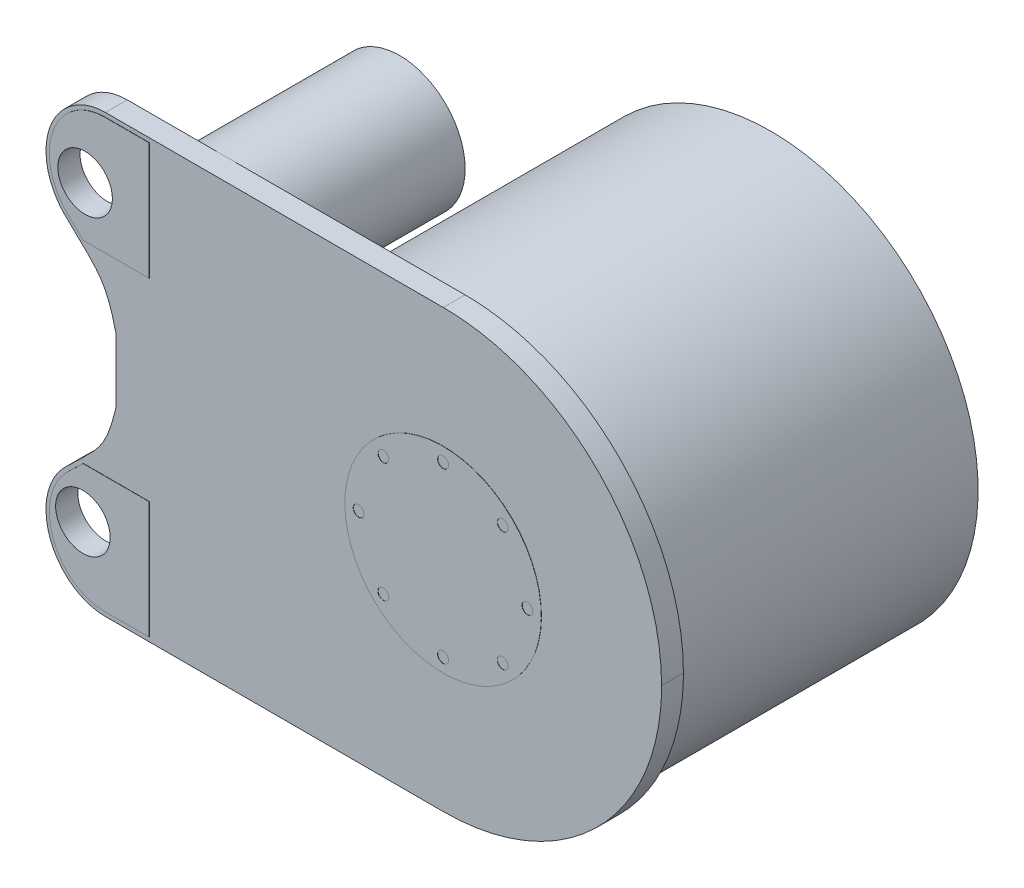
SolidWorks part; units mm, degrees
ref_plane "Plano frontal" through (0, 0, 0) normal (0, 0, 1) x (1, 0, 0)
ref_plane "Plano superior" through (0, 0, 0) normal (0, 1, 0) x (1, 0, 0)
ref_plane "Plano direito" through (0, 0, 0) normal (1, 0, 0) x (0, 0, -1)
sketch "Esboço1" plane through (0, 0, 0) normal (0, 0, 1) x (1, 0, 0)
  line L0 (-10.9, 1.5) -> (-10.9, 1.4998)
  line L1 (-10.9, -1.4998) -> (-10.9, -1.5)
  line L2 (-11.375, -9.9996) -> (-10.1, -9.9996)
  line L3 (-10.1, -9.9996) -> (4.1, -9.9996)
  line L4 (4.1, 9.9996) -> (-10.1, 9.9996)
  line L5 (-10.1, 9.9996) -> (-11.375, 9.9996)
  ellipse E0 centre (4.1, -0.0004) end of major axis (4.1, 9.4996) minor radius 9.5
  ellipse E1 centre (-12.3, 6.7497) end of major axis (-12.3, 7.9997) minor radius 1.25
  ellipse E2 centre (-12.4, -6.7497) end of major axis (-11.15, -6.7497) minor radius 1.2499
  ellipse E5 centre (4.1, -0.0004) end of major axis (4.1, 8.4996) minor radius 8.5
  spline S0 degree 3 poles (-11.375, 9.9996) (-12.8799, 9.9996) (-14.1, 8.7075) (-14.1, 7.1137) knots 0 0 0 0 0.05 0.05 0.05 0.05
  spline S1 degree 3 poles (-14.1, 7.1137) (-14.1, 6.3284) (-13.8037, 5.6164) (-13.3233, 5.0962) knots 0.05 0.05 0.05 0.05 0.1 0.1 0.1 0.1
  spline S2 degree 3 poles (-13.3233, 5.0962) (-13.3196, 5.092) (-13.3154, 5.0875) (-13.3114, 5.0835) knots 0.1 0.1 0.1 0.1 0.15 0.15 0.15 0.15
  spline S3 degree 3 poles (-13.3114, 5.0835) (-13.2765, 5.0461) (-13.2405, 5.0095) (-13.2036, 4.9741) knots 0.15 0.15 0.15 0.15 0.2 0.2 0.2 0.2
  spline S4 degree 3 poles (-13.2036, 4.9741) (-11.7596, 3.5417) (-11.3715, 3.4497) (-10.9, 1.5) knots 0.2 0.2 0.2 0.2 0.25 0.25 0.25 0.25
  spline S5 degree 3 poles (-10.9, 1.4998) (-10.9, 0.5) (-10.9, -0.5) (-10.9, -1.4998) knots 0.3 0.3 0.3 0.3 0.35 0.35 0.35 0.35
  spline S6 degree 3 poles (-10.9, -1.5) (-11.3712, -3.4492) (-11.761, -3.5431) (-13.2036, -4.9741) knots 0.4 0.4 0.4 0.4 0.45 0.45 0.45 0.45
  spline S7 degree 3 poles (-13.2036, -4.9741) (-13.2369, -5.006) (-13.2695, -5.0389) (-13.3011, -5.0725) knots 0.45 0.45 0.45 0.45 0.5 0.5 0.5 0.5
  spline S8 degree 3 poles (-13.3011, -5.0725) (-13.3105, -5.0824) (-13.3196, -5.0921) (-13.3287, -5.1021) knots 0.5 0.5 0.5 0.5 0.55 0.55 0.55 0.55
  spline S9 degree 3 poles (-13.3287, -5.1021) (-13.8059, -5.6217) (-14.1, -6.3313) (-14.1, -7.1137) knots 0.55 0.55 0.55 0.55 0.6 0.6 0.6 0.6
  spline S10 degree 3 poles (-14.1, -7.1137) (-14.1, -8.7075) (-12.8799, -9.9996) (-11.375, -9.9996) knots 0.6 0.6 0.6 0.6 0.65 0.65 0.65 0.65
  spline S11 degree 3 poles (4.1, -9.9996) (9.6228, -9.9996) (14.1, -5.5226) (14.1, 0) knots 0.75 0.75 0.75 0.75 0.8 0.8 0.8 0.8
  spline S12 degree 3 poles (14.1, 0) (14.1, 5.5226) (9.6228, 9.9996) (4.1, 9.9996) knots 0.8 0.8 0.8 0.8 0.85 0.85 0.85 0.85
  point P56 (-6.9, 6.9997)
  ellipse B0 centre (-6.9, 6.9997) end of major axis (-3.9, 6.9997) minor radius 2.9999
  ellipse B1 centre (-6.9, 6.9997) end of major axis (-9.15, 6.9997) minor radius 2.25
sketch_block_instance "Bloco1-1"
sketch_block "Bloco1"
extrude "Ressalto-extrusão1" add sketch "Esboço1" along normal blind 1 contours L4 L5 S0 S1 S2 S3 S4 L0 S5 L1 S6 S7 S8 S9 S10 L2 L3 S11 S12
ref_plane "Plano2" through (0, 0, 1) normal (0, 0, 1) x (1, 0, 0)
sketch "Esboço3" plane through (0, 0, 1) normal (0, 0, 1) x (1, 0, 0)
  line L0 (-12.3882, 4.4299) -> (-9.3652, 4.4299)
  line L1 (-9.3652, 4.4299) -> (-9.3652, 9.8065)
  line L2 (-9.3652, 9.8065) -> (-10.2039, 9.8065)
  line L3 (-10.2039, 9.8065) -> (-11.3935, 9.8065)
  line L4 (-12.3882, -4.4299) -> (-9.3652, -4.4299)
  line L5 (-9.3652, -4.4299) -> (-9.3652, -9.8065)
  line L6 (-9.3652, -9.8065) -> (-10.2039, -9.8065)
  line L7 (-10.2039, -9.8065) -> (-11.3935, -9.8065)
  ellipse E0 centre (4.1, -0.0004) end of major axis (4.1, 4.4996) minor radius 4.5
  ellipse E1 centre (4.1, 3.8664) end of major axis (3.85, 3.8664) minor radius 0.25
  spline S0 degree 3 poles (-11.3935, 9.8065) (-12.7975, 9.8065) (-13.9358, 8.601) (-13.9358, 7.114) knots 0 0 0 0 0.1 0.1 0.1 0.1
  spline S1 degree 3 poles (-13.9358, 7.114) (-13.9358, 6.3813) (-13.6594, 5.717) (-13.2112, 5.2317) knots 0.1 0.1 0.1 0.1 0.2 0.2 0.2 0.2
  spline S2 degree 3 poles (-13.2112, 5.2317) (-13.2077, 5.2278) (-13.2038, 5.2236) (-13.2001, 5.2199) knots 0.2 0.2 0.2 0.2 0.3 0.3 0.3 0.3
  spline S3 degree 3 poles (-13.2001, 5.2199) (-13.1675, 5.185) (-13.1339, 5.1508) (-13.0995, 5.1178) knots 0.3 0.3 0.3 0.3 0.4 0.4 0.4 0.4
  spline S4 degree 3 poles (-13.0995, 5.1178) (-12.8243, 4.8448) (-12.5903, 4.624) (-12.3882, 4.4299) knots 0.4 0.4 0.4 0.4 0.5 0.5 0.5 0.5
  spline S5 degree 3 poles (-11.3935, -9.8065) (-12.7975, -9.8065) (-13.9358, -8.601) (-13.9358, -7.114) knots 0 0 0 0 0.1 0.1 0.1 0.1
  spline S6 degree 3 poles (-13.9358, -7.114) (-13.9358, -6.3813) (-13.6594, -5.717) (-13.2112, -5.2317) knots 0.1 0.1 0.1 0.1 0.2 0.2 0.2 0.2
  spline S7 degree 3 poles (-13.2112, -5.2317) (-13.2077, -5.2278) (-13.2038, -5.2236) (-13.2001, -5.2199) knots 0.2 0.2 0.2 0.2 0.3 0.3 0.3 0.3
  spline S8 degree 3 poles (-13.2001, -5.2199) (-13.1675, -5.185) (-13.1339, -5.1508) (-13.0995, -5.1178) knots 0.3 0.3 0.3 0.3 0.4 0.4 0.4 0.4
  spline S9 degree 3 poles (-13.0995, -5.1178) (-12.8243, -4.8448) (-12.5903, -4.624) (-12.3882, -4.4299) knots 0.4 0.4 0.4 0.4 0.5 0.5 0.5 0.5
  spline S10 degree 3 poles (7.011, 2.9106) (7.1086, 2.813) (7.1086, 2.6547) (7.011, 2.5571) knots 0 0 0 0 0.2 0.2 0.2 0.2
  spline S11 degree 3 poles (7.011, 2.5571) (6.9134, 2.4594) (6.7551, 2.4594) (6.6575, 2.5571) knots 0.2 0.2 0.2 0.2 0.4 0.4 0.4 0.4
  spline S12 degree 3 poles (6.6575, 2.5571) (6.5598, 2.6547) (6.5598, 2.813) (6.6575, 2.9106) knots 0.4 0.4 0.4 0.4 0.6 0.6 0.6 0.6
  spline S13 degree 3 poles (6.6575, 2.9106) (6.7551, 3.0082) (6.9134, 3.0082) (7.011, 2.9106) knots 0.6 0.6 0.6 0.6 1 1 1 1
  spline S14 degree 3 poles (8.2168, -0.0004) (8.2168, -0.1385) (8.1049, -0.2504) (7.9668, -0.2504) knots 0 0 0 0 0.2 0.2 0.2 0.2
  spline S15 degree 3 poles (7.9668, -0.2504) (7.8287, -0.2504) (7.7168, -0.1385) (7.7168, -0.0004) knots 0.2 0.2 0.2 0.2 0.4 0.4 0.4 0.4
  spline S16 degree 3 poles (7.7168, -0.0004) (7.7168, 0.1377) (7.8287, 0.2496) (7.9668, 0.2496) knots 0.4 0.4 0.4 0.4 0.6 0.6 0.6 0.6
  spline S17 degree 3 poles (7.9668, 0.2496) (8.1049, 0.2496) (8.2168, 0.1377) (8.2168, -0.0004) knots 0.6 0.6 0.6 0.6 1 1 1 1
  spline S18 degree 3 poles (7.011, -2.9114) (6.9134, -3.009) (6.7551, -3.009) (6.6575, -2.9114) knots 0 0 0 0 0.2 0.2 0.2 0.2
  spline S19 degree 3 poles (6.6575, -2.9114) (6.5598, -2.8138) (6.5598, -2.6555) (6.6575, -2.5579) knots 0.2 0.2 0.2 0.2 0.4 0.4 0.4 0.4
  spline S20 degree 3 poles (6.6575, -2.5579) (6.7551, -2.4602) (6.9134, -2.4602) (7.011, -2.5579) knots 0.4 0.4 0.4 0.4 0.6 0.6 0.6 0.6
  spline S21 degree 3 poles (7.011, -2.5579) (7.1086, -2.6555) (7.1086, -2.8138) (7.011, -2.9114) knots 0.6 0.6 0.6 0.6 1 1 1 1
  spline S22 degree 3 poles (4.1, -4.1172) (3.9619, -4.1172) (3.85, -4.0053) (3.85, -3.8672) knots 0 0 0 0 0.2 0.2 0.2 0.2
  spline S23 degree 3 poles (3.85, -3.8672) (3.85, -3.7291) (3.9619, -3.6172) (4.1, -3.6172) knots 0.2 0.2 0.2 0.2 0.4 0.4 0.4 0.4
  spline S24 degree 3 poles (4.1, -3.6172) (4.2381, -3.6172) (4.35, -3.7291) (4.35, -3.8672) knots 0.4 0.4 0.4 0.4 0.6 0.6 0.6 0.6
  spline S25 degree 3 poles (4.35, -3.8672) (4.35, -4.0053) (4.2381, -4.1172) (4.1, -4.1172) knots 0.6 0.6 0.6 0.6 1 1 1 1
  spline S26 degree 3 poles (1.189, -2.9114) (1.0914, -2.8138) (1.0914, -2.6555) (1.189, -2.5579) knots 0 0 0 0 0.2 0.2 0.2 0.2
  spline S27 degree 3 poles (1.189, -2.5579) (1.2866, -2.4602) (1.4449, -2.4602) (1.5425, -2.5579) knots 0.2 0.2 0.2 0.2 0.4 0.4 0.4 0.4
  spline S28 degree 3 poles (1.5425, -2.5579) (1.6402, -2.6555) (1.6402, -2.8138) (1.5425, -2.9114) knots 0.4 0.4 0.4 0.4 0.6 0.6 0.6 0.6
  spline S29 degree 3 poles (1.5425, -2.9114) (1.4449, -3.009) (1.2866, -3.009) (1.189, -2.9114) knots 0.6 0.6 0.6 0.6 1 1 1 1
  spline S30 degree 3 poles (-0.0168, -0.0004) (-0.0168, 0.1377) (0.0951, 0.2496) (0.2332, 0.2496) knots 0 0 0 0 0.2 0.2 0.2 0.2
  spline S31 degree 3 poles (0.2332, 0.2496) (0.3713, 0.2496) (0.4832, 0.1377) (0.4832, -0.0004) knots 0.2 0.2 0.2 0.2 0.4 0.4 0.4 0.4
  spline S32 degree 3 poles (0.4832, -0.0004) (0.4832, -0.1385) (0.3713, -0.2504) (0.2332, -0.2504) knots 0.4 0.4 0.4 0.4 0.6 0.6 0.6 0.6
  spline S33 degree 3 poles (0.2332, -0.2504) (0.0951, -0.2504) (-0.0168, -0.1385) (-0.0168, -0.0004) knots 0.6 0.6 0.6 0.6 1 1 1 1
  spline S34 degree 3 poles (1.189, 2.9106) (1.2866, 3.0082) (1.4449, 3.0082) (1.5425, 2.9106) knots 0 0 0 0 0.2 0.2 0.2 0.2
  spline S35 degree 3 poles (1.5425, 2.9106) (1.6402, 2.813) (1.6402, 2.6547) (1.5425, 2.5571) knots 0.2 0.2 0.2 0.2 0.4 0.4 0.4 0.4
  spline S36 degree 3 poles (1.5425, 2.5571) (1.4449, 2.4594) (1.2866, 2.4594) (1.189, 2.5571) knots 0.4 0.4 0.4 0.4 0.6 0.6 0.6 0.6
  spline S37 degree 3 poles (1.189, 2.5571) (1.0914, 2.6547) (1.0914, 2.813) (1.189, 2.9106) knots 0.6 0.6 0.6 0.6 1 1 1 1
extrude "Ressalto-extrusão8" add sketch "Esboço3" along normal blind 0.01
extrude "Corte-extrusão1" cut sketch "Esboço1<3>" along normal blind 1.5 contours E1 | E2
sketch "Esboço1<3>" plane through (0, 0, 0) normal (0, 0, 1) x (1, 0, 0) same geometry as "Esboço1"
extrude "Ressalto-extrusão2" add sketch "Esboço1<4>" against normal blind 14 contours E0 | E5
sketch "Esboço1<4>" plane through (0, 0, 0) normal (0, 0, 1) x (1, 0, 0) same geometry as "Esboço1"
extrude "Ressalto-extrusão3" add sketch "Esboço1<5>" against normal blind 8 contours B0 | B1
sketch "Esboço1<5>" plane through (0, 0, 0) normal (0, 0, 1) x (1, 0, 0) same geometry as "Esboço1"
extrude "Ressalto-extrusão4" add sketch "Esboço1<6>" against normal blind 11.5 contours E5
sketch "Esboço1<6>" plane through (0, 0, 0) normal (0, 0, 1) x (1, 0, 0) same geometry as "Esboço1"
extrude "Ressalto-extrusão5" add sketch "Esboço1<7>" against normal blind 6.5 contours B1
sketch "Esboço1<7>" plane through (0, 0, 0) normal (0, 0, 1) x (1, 0, 0) same geometry as "Esboço1"
sketch "Esboço4" plane through (0, 0, 0) normal (0, 0, 1) x (1, 0, 0)
  line L0 (-12.3882, 4.4299) -> (-9.3652, 4.4299)
  line L1 (-9.3652, 4.4299) -> (-9.3652, 9.8065)
  line L2 (-9.3652, 9.8065) -> (-10.2039, 9.8065)
  line L3 (-10.2039, 9.8065) -> (-11.3935, 9.8065)
  line L4 (-12.3882, -4.4299) -> (-9.3652, -4.4299)
  line L5 (-9.3652, -4.4299) -> (-9.3652, -9.8065)
  line L6 (-9.3652, -9.8065) -> (-10.2039, -9.8065)
  line L7 (-10.2039, -9.8065) -> (-11.3935, -9.8065)
  spline S0 degree 3 poles (-11.3935, 9.8065) (-12.7975, 9.8065) (-13.9358, 8.601) (-13.9358, 7.114) knots 0 0 0 0 0.1 0.1 0.1 0.1
  spline S1 degree 3 poles (-13.9358, 7.114) (-13.9358, 6.3813) (-13.6594, 5.717) (-13.2112, 5.2317) knots 0.1 0.1 0.1 0.1 0.2 0.2 0.2 0.2
  spline S2 degree 3 poles (-13.2112, 5.2317) (-13.2077, 5.2278) (-13.2038, 5.2236) (-13.2001, 5.2199) knots 0.2 0.2 0.2 0.2 0.3 0.3 0.3 0.3
  spline S3 degree 3 poles (-13.2001, 5.2199) (-13.1675, 5.185) (-13.1339, 5.1508) (-13.0995, 5.1178) knots 0.3 0.3 0.3 0.3 0.4 0.4 0.4 0.4
  spline S4 degree 3 poles (-13.0995, 5.1178) (-12.8243, 4.8448) (-12.5903, 4.624) (-12.3882, 4.4299) knots 0.4 0.4 0.4 0.4 0.5 0.5 0.5 0.5
  spline S5 degree 3 poles (-11.3935, -9.8065) (-12.7975, -9.8065) (-13.9358, -8.601) (-13.9358, -7.114) knots 0 0 0 0 0.1 0.1 0.1 0.1
  spline S6 degree 3 poles (-13.9358, -7.114) (-13.9358, -6.3813) (-13.6594, -5.717) (-13.2112, -5.2317) knots 0.1 0.1 0.1 0.1 0.2 0.2 0.2 0.2
  spline S7 degree 3 poles (-13.2112, -5.2317) (-13.2077, -5.2278) (-13.2038, -5.2236) (-13.2001, -5.2199) knots 0.2 0.2 0.2 0.2 0.3 0.3 0.3 0.3
  spline S8 degree 3 poles (-13.2001, -5.2199) (-13.1675, -5.185) (-13.1339, -5.1508) (-13.0995, -5.1178) knots 0.3 0.3 0.3 0.3 0.4 0.4 0.4 0.4
  spline S9 degree 3 poles (-13.0995, -5.1178) (-12.8243, -4.8448) (-12.5903, -4.624) (-12.3882, -4.4299) knots 0.4 0.4 0.4 0.4 0.5 0.5 0.5 0.5
extrude "Ressalto-extrusão11" add sketch "Esboço4" against normal blind 0.01
extrude "Corte-extrusão4" cut sketch "Esboço1<9>" against normal blind 0.5 contours E1 | E2
sketch "Esboço1<9>" plane through (0, 0, 0) normal (0, 0, 1) x (1, 0, 0) same geometry as "Esboço1"
sketch "Sketch1" plane through (0, 0, 0) normal (0, 0, -1) x (-1, 0, 0)
  point P0 (12.3, 6.7497)
  point P1 (12.4, -6.7497)
sketch "Sketch2" plane through (0, 0, 1) normal (0, 0, 1) x (1, 0, 0)
  point P0 (-12.4, -6.7497)
  point P1 (-12.3, 6.7497)
ref_axis "Axis1" through (-12.4, -6.7497, 0) along (0, 0, 1)
ref_axis "Axis2" through (-12.3, 6.7497, 0) along (0, 0, 1)
sketch "Sketch3" plane through (0, 0, -14) normal (0, 0, -1) x (-1, 0, 0)
  point P0 (-4.1, -0.0004)
sketch "Sketch4" plane through (0, 0, -11.5) normal (0, 0, -1) x (-1, 0, 0)
  point P0 (-4.1, -0.0004)
ref_axis "Axis3" through (4.1, -0.0004, -14) along (0, 0, 1)
sketch "Sketch5" plane through (0, 0, -11.5) normal (0, 0, -1) x (-1, 0, 0)
  point P0 (-4.1, -0.0004)
  point P1 (-5.9781, 35.5024)
sketch "Sketch6" plane through (0, 0, 1) normal (0, 0, 1) x (1, 0, 0)
  point P0 (4.1, -0.0004)
ref_axis "Axis4" through (4.1, -0.0004, -11.5) along (0, 0, 1)
